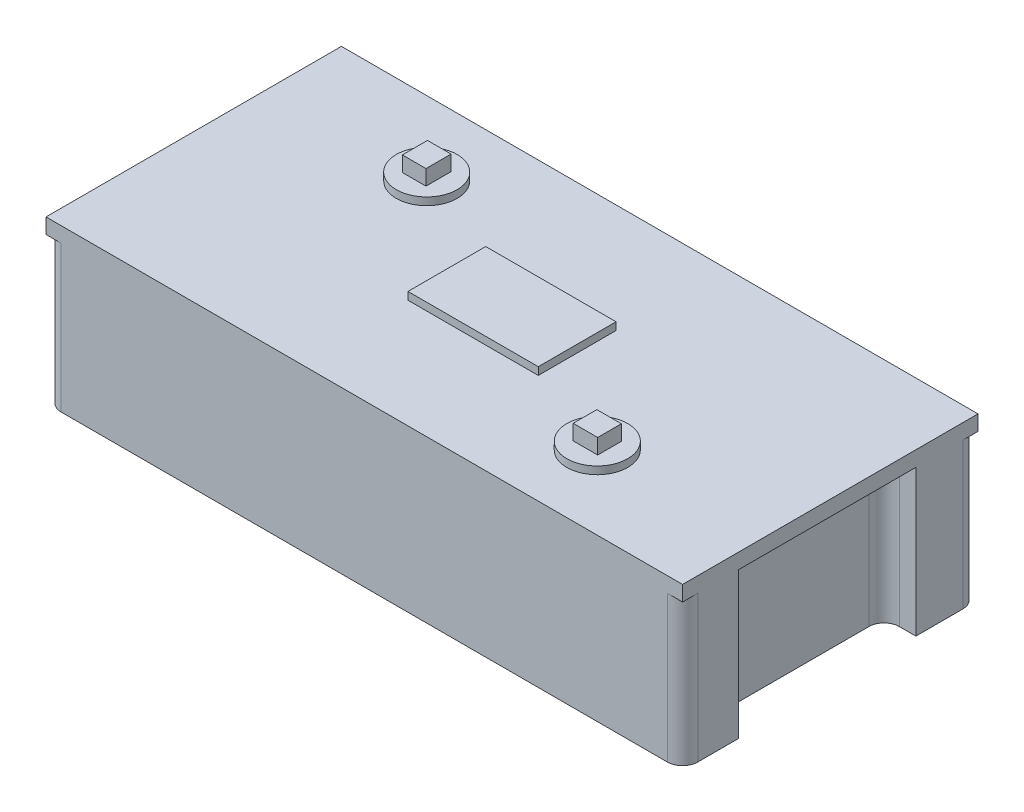
SolidWorks part; units mm, degrees
ref_plane "Front Plane" through (0, 0, 0) normal (0, 0, 1) x (1, 0, 0)
ref_plane "Top Plane" through (0, 0, 0) normal (0, 1, 0) x (1, 0, 0)
ref_plane "Right Plane" through (0, 0, 0) normal (1, 0, 0) x (0, 0, -1)
sketch "Sketch1" plane through (0, 0, 0) normal (0, 1, 0) x (1, 0, 0)
  line L0 (-209, -87) -> (-209, -60.2)
  line L1 (199, 97) -> (-199, 97)
  line L2 (209, 87) -> (209, -87)
  line L3 (199, -97) -> (-199, -97)
  line L4 (-209, 87) -> (-209, -87)
  line L5 (209, 97) -> (-209, -97) construction
  line L6 (209, -97) -> (-209, 97) construction
  line L7 (-209, 87) -> (-209, 61.1692)
  line L8 (-209, 87) -> (-209, 56.2018)
  line L9 (-209, -60.2) -> (-198.1578, -60.2)
  line L10 (-188.1578, -50.2) -> (-188.1578, 46.2018)
  line L11 (-198.1578, 56.2018) -> (-209, 56.2018)
  line L12 (-209, 56.2018) -> (-209, -60.2)
  line L13 (0, 97) -> (0, -97)
  line L14 (209, -60.2) -> (198.1578, -60.2)
  line L15 (198.1578, 56.2018) -> (209, 56.2018)
  line L16 (188.1578, -50.2) -> (188.1578, 46.2018)
  arc A0 (-199, -97) -> (-209, -87) centre (-199, -87) cw
  arc A1 (199, -97) -> (209, -87) centre (199, -87) ccw
  arc A2 (199, 97) -> (209, 87) centre (199, 87) cw
  arc A3 (-199, 97) -> (-209, 87) centre (-199, 87) ccw
  arc A4 (198.1578, 56.2018) -> (188.1578, 46.2018) centre (198.1578, 46.2018) ccw
  arc A5 (198.1578, -60.2) -> (188.1578, -50.2) centre (198.1578, -50.2) cw
  arc A6 (-198.1578, -60.2) -> (-188.1578, -50.2) centre (-198.1578, -50.2) ccw
  arc A7 (-188.1578, 46.2018) -> (-198.1578, 56.2018) centre (-198.1578, 46.2018) ccw
  point P0 (0, 0)
  point P31 (188.1578, 56.2018)
  point P34 (188.1578, -60.2)
  point P37 (-188.1578, -60.2)
  point P40 (-188.1578, 56.2018)
  dimension "D1" = 10
  dimension "D2" = 10
extrude "Boss-Extrude2" add sketch "Sketch1" along normal blind 96 contours A7 L10 A6 L9 L0 A0 L3 L13 L1 A3 L4 L11 | L14 A5 L16 A4 L15 L2 A2 L1 L13 L3 A1 region at (-98.4941, 0, -0.125) region at (98.4941, 0, -0.125)
ref_plane "Top_Plane" through (0, 96, 0) normal (0, 1, 0) x (1, 0, 0)
sketch "Sketch2" plane through (0, 96, 0) normal (0, 1, 0) x (1, 0, 0)
  line L1 (209, 97) -> (-209, 97)
  line L2 (209, 97) -> (209, -97)
  line L3 (209, -97) -> (-209, -97)
  line L4 (-209, 97) -> (-209, -97)
  line L5 (209, 97) -> (-209, -97) construction
  line L6 (209, -97) -> (-209, 97) construction
  point P0 (0, 0)
extrude "Boss-Extrude3" add sketch "Sketch2" along normal blind 10
sketch "Sketch3" plane through (0, 96, 0) normal (0, 1, 0) x (1, 0, 0)
  line L12 (-96.743, 56.7439) -> (-112.257, 56.7439)
  line L13 (-96.743, 56.7439) -> (-96.743, 40.2561)
  line L14 (-96.743, 40.2561) -> (-112.257, 40.2561)
  line L15 (-112.257, 56.7439) -> (-112.257, 40.2561)
  line L16 (-96.743, 56.7439) -> (-112.257, 40.2561) construction
  line L17 (-96.743, 40.2561) -> (-112.257, 56.7439) construction
  line L18 (112.543, -40.7169) -> (96.457, -40.7169)
  line L19 (112.543, -40.7169) -> (112.543, -56.2831)
  line L20 (112.543, -56.2831) -> (96.457, -56.2831)
  line L21 (96.457, -40.7169) -> (96.457, -56.2831)
  line L22 (112.543, -40.7169) -> (96.457, -56.2831) construction
  line L23 (112.543, -56.2831) -> (96.457, -40.7169) construction
  circle A1 centre (-104.5, 48.5) radius 20
  circle A2 centre (104.5, -48.5) radius 20
extrude "Boss-Extrude5" add sketch "Sketch3" along normal blind 15 contours A1
extrude "Boss-Extrude6" add sketch "Sketch3<4>" along normal blind 25 contours L14 L15 L12 L13 | L19 L20 L21 L18
sketch "Sketch3<4>" plane through (0, 96, 0) normal (0, 1, 0) x (1, 0, 0) same geometry as "Sketch3"
extrude "Boss-Extrude7" add sketch "Sketch3<6>" along normal blind 15 contours A2
sketch "Sketch3<6>" plane through (0, 96, 0) normal (0, 1, 0) x (1, 0, 0) same geometry as "Sketch3"
sketch "Sketch4" plane through (0, 96, 0) normal (0, 1, 0) x (1, 0, 0)
  line L1 (42.7865, 25.5339) -> (-42.7865, 25.5339)
  line L2 (42.7865, 25.5339) -> (42.7865, -25.5339)
  line L3 (42.7865, -25.5339) -> (-42.7865, -25.5339)
  line L4 (-42.7865, 25.5339) -> (-42.7865, -25.5339)
  line L5 (42.7865, 25.5339) -> (-42.7865, -25.5339) construction
  line L6 (42.7865, -25.5339) -> (-42.7865, 25.5339) construction
  point P0 (0, 0)
extrude "Boss-Extrude8" add sketch "Sketch4" along normal blind 15
